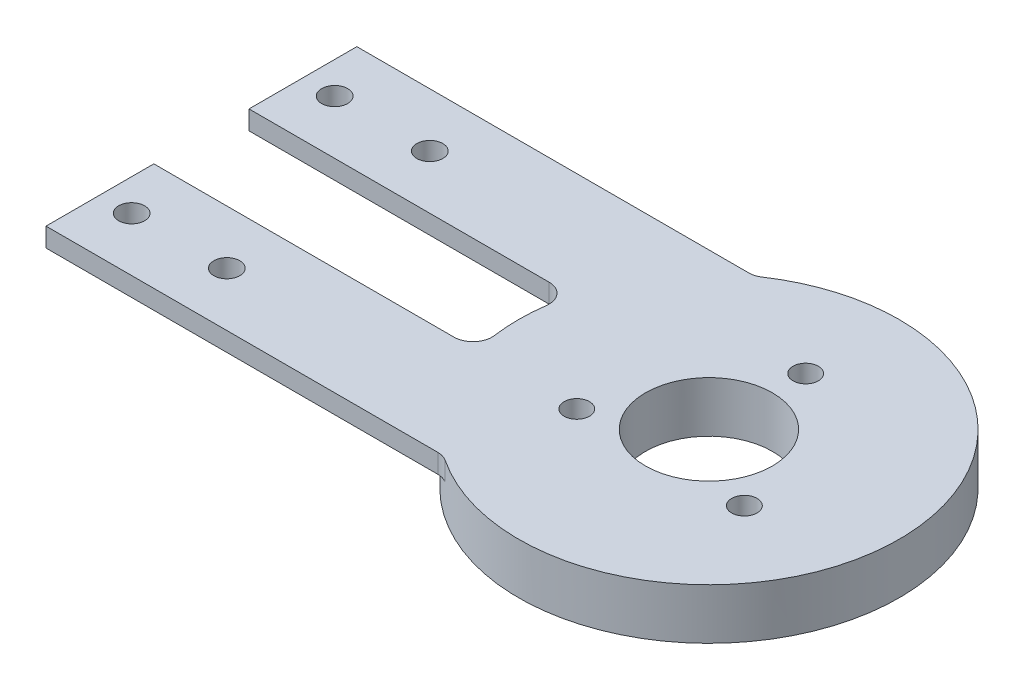
SolidWorks part; units mm, degrees
ref_plane "Front Plane" through (0, 0, 0) normal (0, 0, 1) x (1, 0, 0)
ref_plane "Top Plane" through (0, 0, 0) normal (0, 1, 0) x (1, 0, 0)
ref_plane "Right Plane" through (0, 0, 0) normal (1, 0, 0) x (0, 0, -1)
sketch "Sketch1" plane through (0, 0, 0) normal (0, 1, 0) x (1, 0, 0)
  circle A0 centre (0, 0) radius 30
  circle A1 centre (0, 0) radius 10
  circle A2 centre (0, 0) radius 15.25 construction
  circle A3 centre (0, 15.25) radius 2
  circle A4 centre (13.2069, -7.625) radius 2
  circle A5 centre (-13.2069, -7.625) radius 2
  point P13 (0, 0)
  dimension "D1" = 30.5
  dimension "D2" = 60
  dimension "D3" = 20
  dimension "D4" = 4
  dimension "D5" = 3
extrude "Boss-Extrude1" add sketch "Sketch1" along normal blind 3
sketch "Sketch2" plane through (0, 3, 0) normal (0, 1, 0) x (1, 0, 0)
  line L1 (-80, 24.5) -> (-17, 24.5)
  line L2 (-80, 24.5) -> (-80, 7.5)
  line L3 (-80, 7.5) -> (-17, 7.5)
  line L4 (-17, 24.5) -> (-17, 7.5)
  line L5 (-80, -7.5) -> (-17, -7.5)
  line L6 (-80, -7.5) -> (-80, -24.5)
  line L7 (-80, -24.5) -> (-17, -24.5)
  line L8 (-17, -7.5) -> (-17, -24.5)
  circle A0 centre (0, 0) radius 10 construction
  dimension "D1" = 17
  dimension "D2" = 15
  dimension "D3" = 7.5
  dimension "D4" = 17
  dimension "D5" = 80
extrude "Boss-Extrude2" add sketch "Sketch2" against normal up to surface (3 mm away) up to face at (0, 0, 30)
sketch "Sketch3" plane through (0, 0, 0) normal (0, -1, 0) x (1, 0, 0)
  circle A0 centre (0, 0) radius 30
  arc A1 (-17.3133, -24.5) -> (-17.3133, 24.5) centre (0, 0) ccw construction
  circle A2 centre (0, -15.25) radius 2 construction
  circle A3 centre (13.2069, 7.625) radius 2 construction
  circle A4 centre (-13.2069, 7.625) radius 2 construction
  circle A5 centre (0, 0) radius 10 construction
  circle A6 centre (0, -15.25) radius 2
  circle A7 centre (13.2069, 7.625) radius 2
  circle A8 centre (-13.2069, 7.625) radius 2
  circle A9 centre (0, 0) radius 10
extrude "Boss-Extrude3" add sketch "Sketch3" along normal blind 5
sketch "Sketch4" plane through (0, 0, 0) normal (0, -1, 0) x (1, 0, 0)
  line L0 (-80, 24.5) -> (-80, 7.5) construction
  line L1 (-80, 7.5) -> (-29.0474, 7.5) construction
  line L2 (-80, -24.5) -> (-17.3133, -24.5) construction
  circle A0 centre (-75, 16) radius 2.05
  circle A1 centre (-60, 16) radius 2.05
  circle A2 centre (-75, -16) radius 2.05
  circle A3 centre (-60, -16) radius 2.05
  dimension "D1" = 4.1
  dimension "D2" = 5
  dimension "D3" = 15
  dimension "D4" = 8.5
  dimension "D5" = 8.5
extrude "Cut-Extrude1" cut sketch "Sketch4" against normal through all
fillet "Fillet1" radius 3 4 edges at (-17.3133, 1.5, -24.5) (-29.0474, 1.5, -7.5) (-29.0474, 1.5, 7.5) (-17.3133, 1.5, 24.5)
